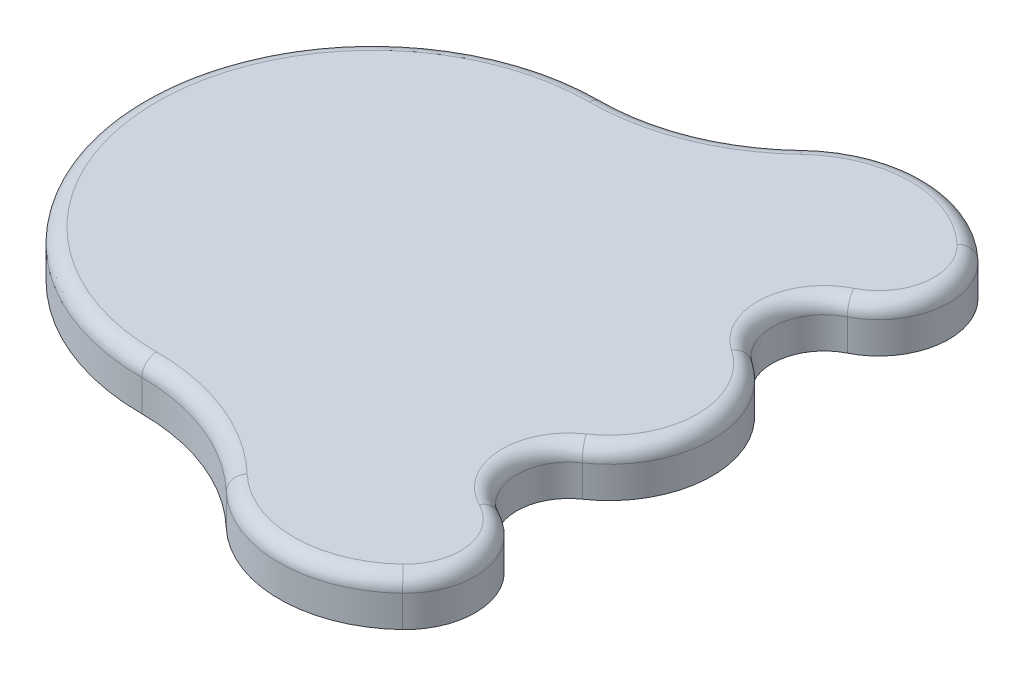
SolidWorks part; units mm, degrees
ref_plane "Front Plane" through (0, 0, 0) normal (0, 0, 1) x (1, 0, 0)
ref_plane "Top Plane" through (0, 0, 0) normal (0, 1, 0) x (1, 0, 0)
ref_plane "Right Plane" through (0, 0, 0) normal (1, 0, 0) x (0, 0, -1)
sketch "Sketch1" plane through (0, 0, 0) normal (0, 1, 0) x (1, 0, 0)
  line L0 (0, 31.75) -> (0, -31.75) construction
  line L1 (31.75, 0) -> (-31.75, 0) construction
  line L2 (46.5723, 0) -> (38.4474, 0) construction
  line L3 (46.5723, 32.5311) -> (46.5723, -32.5311) construction
  circle A0 centre (0, 0) radius 31.75
  arc A1 (0, 31.75) -> (19.3619, 39.5051) centre (0, 59.7976) ccw
  arc A2 (19.3619, 39.5051) -> (43.5872, 39.5051) centre (31.4746, 26.8103) cw
  arc A3 (43.5872, 39.5051) -> (41.2373, 23.9062) centre (36.933, 32.5311) cw
  arc A4 (41.2373, 23.9062) -> (40.4072, 11.6637) centre (44.4137, 17.5414) ccw
  arc A5 (40.4072, 11.6637) -> (40.4072, -11.6637) centre (32.4566, 0) cw
  arc A6 (41.2373, -23.9062) -> (40.4072, -11.6637) centre (44.4137, -17.5414) cw
  arc A7 (43.5872, -39.5051) -> (41.2373, -23.9062) centre (36.933, -32.5311) ccw
  arc A8 (19.3619, -39.5051) -> (43.5872, -39.5051) centre (31.4746, -26.8103) ccw
  arc A9 (0, -31.75) -> (19.3619, -39.5051) centre (0, -59.7976) cw
  dimension "D1" = 63.5
extrude "Boss-Extrude1" add sketch "Sketch1" along normal blind 6.35 contours A0 | A0 A9 A8 A7 A6 A5 A4 A3 A2 A1 region at (0, 0, 0) region at (23.1591, 0, -23.1591)
fillet "Fillet1" radius 2.032 10 edges at (10.4286, 6.35, -33.7609) (31.4746, 6.35, -44.3567) (46.4648, 6.35, -31.0952) (37.3166, 6.35, -18.0227) (46.5723, 6.35, 0) (37.3166, 6.35, 18.0227) (46.4648, 6.35, 31.0952) (31.4746, 6.35, 44.3567) (10.4286, 6.35, 33.7609) (-31.75, 6.35, 0)
